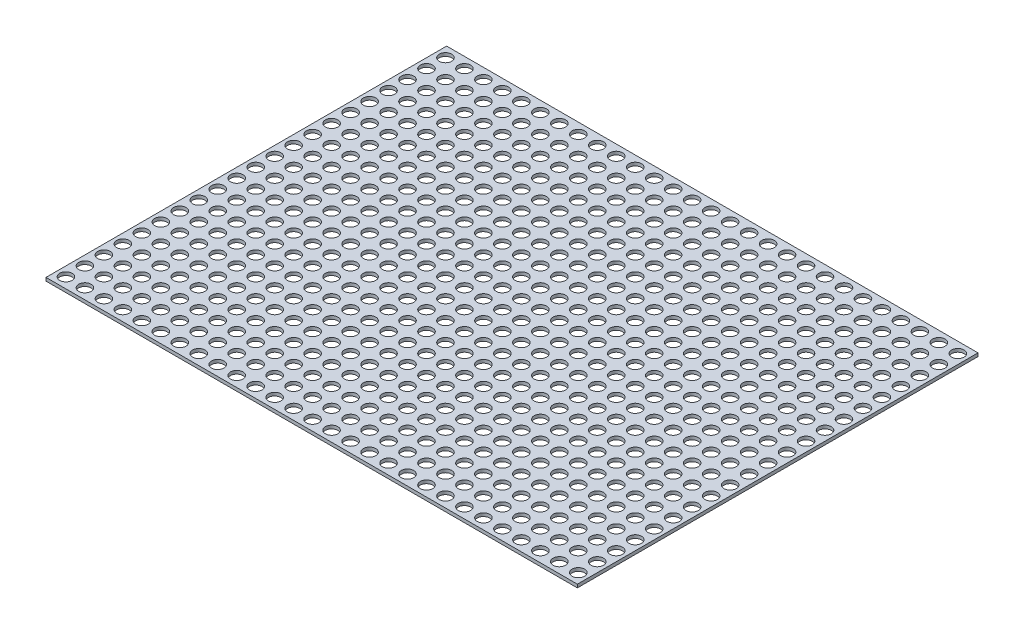
SolidWorks part; units mm, degrees
ref_plane "Front Plane" through (0, 0, 0) normal (0, 0, 1) x (1, 0, 0)
ref_plane "Top Plane" through (0, 0, 0) normal (0, 1, 0) x (1, 0, 0)
ref_plane "Right Plane" through (0, 0, 0) normal (1, 0, 0) x (0, 0, -1)
sketch "Sketch1" plane through (0, 0, 0) normal (0, 1, 0) x (1, 0, 0)
  line L0 (4.5, 4.95) -> (13.5, 4.95) construction
  line L1 (0, 0) -> (252, 0)
  line L2 (0, 0) -> (0, 190)
  line L3 (0, 190) -> (252, 190)
  line L4 (252, 0) -> (252, 190)
  line L5 (4.5, 4.95) -> (4.5, 13.95) construction
  circle A0 centre (4.5, 4.95) radius 2.95
  circle A1 centre (13.5, 4.95) radius 2.95
  circle A2 centre (22.5, 4.95) radius 2.95
  circle A3 centre (31.5, 4.95) radius 2.95
  circle A4 centre (40.5, 4.95) radius 2.95
  circle A5 centre (49.5, 4.95) radius 2.95
  circle A6 centre (58.5, 4.95) radius 2.95
  circle A7 centre (67.5, 4.95) radius 2.95
  circle A8 centre (76.5, 4.95) radius 2.95
  circle A9 centre (85.5, 4.95) radius 2.95
  circle A10 centre (94.5, 4.95) radius 2.95
  circle A11 centre (103.5, 4.95) radius 2.95
  circle A12 centre (112.5, 4.95) radius 2.95
  circle A13 centre (121.5, 4.95) radius 2.95
  circle A14 centre (130.5, 4.95) radius 2.95
  circle A15 centre (139.5, 4.95) radius 2.95
  circle A16 centre (148.5, 4.95) radius 2.95
  circle A17 centre (157.5, 4.95) radius 2.95
  circle A18 centre (166.5, 4.95) radius 2.95
  circle A19 centre (175.5, 4.95) radius 2.95
  circle A20 centre (184.5, 4.95) radius 2.95
  circle A21 centre (193.5, 4.95) radius 2.95
  circle A22 centre (202.5, 4.95) radius 2.95
  circle A23 centre (211.5, 4.95) radius 2.95
  circle A24 centre (220.5, 4.95) radius 2.95
  circle A25 centre (229.5, 4.95) radius 2.95
  circle A26 centre (238.5, 4.95) radius 2.95
  circle A27 centre (247.5, 4.95) radius 2.95
  circle A28 centre (13.5, 13.95) radius 2.95
  circle A29 centre (22.5, 13.95) radius 2.95
  circle A30 centre (31.5, 13.95) radius 2.95
  circle A31 centre (40.5, 13.95) radius 2.95
  circle A32 centre (49.5, 13.95) radius 2.95
  circle A33 centre (58.5, 13.95) radius 2.95
  circle A34 centre (67.5, 13.95) radius 2.95
  circle A35 centre (76.5, 13.95) radius 2.95
  circle A36 centre (85.5, 13.95) radius 2.95
  circle A37 centre (94.5, 13.95) radius 2.95
  circle A38 centre (103.5, 13.95) radius 2.95
  circle A39 centre (112.5, 13.95) radius 2.95
  circle A40 centre (121.5, 13.95) radius 2.95
  circle A41 centre (130.5, 13.95) radius 2.95
  circle A42 centre (139.5, 13.95) radius 2.95
  circle A43 centre (148.5, 13.95) radius 2.95
  circle A44 centre (157.5, 13.95) radius 2.95
  circle A45 centre (166.5, 13.95) radius 2.95
  circle A46 centre (175.5, 13.95) radius 2.95
  circle A47 centre (184.5, 13.95) radius 2.95
  circle A48 centre (193.5, 13.95) radius 2.95
  circle A49 centre (202.5, 13.95) radius 2.95
  circle A50 centre (211.5, 13.95) radius 2.95
  circle A51 centre (220.5, 13.95) radius 2.95
  circle A52 centre (229.5, 13.95) radius 2.95
  circle A53 centre (238.5, 13.95) radius 2.95
  circle A54 centre (247.5, 13.95) radius 2.95
  circle A55 centre (13.5, 22.95) radius 2.95
  circle A56 centre (22.5, 22.95) radius 2.95
  circle A57 centre (31.5, 22.95) radius 2.95
  circle A58 centre (40.5, 22.95) radius 2.95
  circle A59 centre (49.5, 22.95) radius 2.95
  circle A60 centre (58.5, 22.95) radius 2.95
  circle A61 centre (67.5, 22.95) radius 2.95
  circle A62 centre (76.5, 22.95) radius 2.95
  circle A63 centre (85.5, 22.95) radius 2.95
  circle A64 centre (94.5, 22.95) radius 2.95
  circle A65 centre (103.5, 22.95) radius 2.95
  circle A66 centre (112.5, 22.95) radius 2.95
  circle A67 centre (121.5, 22.95) radius 2.95
  circle A68 centre (130.5, 22.95) radius 2.95
  circle A69 centre (139.5, 22.95) radius 2.95
  circle A70 centre (148.5, 22.95) radius 2.95
  circle A71 centre (157.5, 22.95) radius 2.95
  circle A72 centre (166.5, 22.95) radius 2.95
  circle A73 centre (175.5, 22.95) radius 2.95
  circle A74 centre (184.5, 22.95) radius 2.95
  circle A75 centre (193.5, 22.95) radius 2.95
  circle A76 centre (202.5, 22.95) radius 2.95
  circle A77 centre (211.5, 22.95) radius 2.95
  circle A78 centre (220.5, 22.95) radius 2.95
  circle A79 centre (229.5, 22.95) radius 2.95
  circle A80 centre (238.5, 22.95) radius 2.95
  circle A81 centre (247.5, 22.95) radius 2.95
  circle A82 centre (13.5, 31.95) radius 2.95
  circle A83 centre (22.5, 31.95) radius 2.95
  circle A84 centre (31.5, 31.95) radius 2.95
  circle A85 centre (40.5, 31.95) radius 2.95
  circle A86 centre (49.5, 31.95) radius 2.95
  circle A87 centre (58.5, 31.95) radius 2.95
  circle A88 centre (67.5, 31.95) radius 2.95
  circle A89 centre (76.5, 31.95) radius 2.95
  circle A90 centre (85.5, 31.95) radius 2.95
  circle A91 centre (94.5, 31.95) radius 2.95
  circle A92 centre (103.5, 31.95) radius 2.95
  circle A93 centre (112.5, 31.95) radius 2.95
  circle A94 centre (121.5, 31.95) radius 2.95
  circle A95 centre (130.5, 31.95) radius 2.95
  circle A96 centre (139.5, 31.95) radius 2.95
  circle A97 centre (148.5, 31.95) radius 2.95
  circle A98 centre (157.5, 31.95) radius 2.95
  circle A99 centre (166.5, 31.95) radius 2.95
  circle A100 centre (175.5, 31.95) radius 2.95
  circle A101 centre (184.5, 31.95) radius 2.95
  circle A102 centre (193.5, 31.95) radius 2.95
  circle A103 centre (202.5, 31.95) radius 2.95
  circle A104 centre (211.5, 31.95) radius 2.95
  circle A105 centre (220.5, 31.95) radius 2.95
  circle A106 centre (229.5, 31.95) radius 2.95
  circle A107 centre (238.5, 31.95) radius 2.95
  circle A108 centre (247.5, 31.95) radius 2.95
  circle A109 centre (13.5, 40.95) radius 2.95
  circle A110 centre (22.5, 40.95) radius 2.95
  circle A111 centre (31.5, 40.95) radius 2.95
  circle A112 centre (40.5, 40.95) radius 2.95
  circle A113 centre (49.5, 40.95) radius 2.95
  circle A114 centre (58.5, 40.95) radius 2.95
  circle A115 centre (67.5, 40.95) radius 2.95
  circle A116 centre (76.5, 40.95) radius 2.95
  circle A117 centre (85.5, 40.95) radius 2.95
  circle A118 centre (94.5, 40.95) radius 2.95
  circle A119 centre (103.5, 40.95) radius 2.95
  circle A120 centre (112.5, 40.95) radius 2.95
  circle A121 centre (121.5, 40.95) radius 2.95
  circle A122 centre (130.5, 40.95) radius 2.95
  circle A123 centre (139.5, 40.95) radius 2.95
  circle A124 centre (148.5, 40.95) radius 2.95
  circle A125 centre (157.5, 40.95) radius 2.95
  circle A126 centre (166.5, 40.95) radius 2.95
  circle A127 centre (175.5, 40.95) radius 2.95
  circle A128 centre (184.5, 40.95) radius 2.95
  circle A129 centre (193.5, 40.95) radius 2.95
  circle A130 centre (202.5, 40.95) radius 2.95
  circle A131 centre (211.5, 40.95) radius 2.95
  circle A132 centre (220.5, 40.95) radius 2.95
  circle A133 centre (229.5, 40.95) radius 2.95
  circle A134 centre (238.5, 40.95) radius 2.95
  circle A135 centre (247.5, 40.95) radius 2.95
  circle A136 centre (13.5, 49.95) radius 2.95
  circle A137 centre (22.5, 49.95) radius 2.95
  circle A138 centre (31.5, 49.95) radius 2.95
  circle A139 centre (40.5, 49.95) radius 2.95
  circle A140 centre (49.5, 49.95) radius 2.95
  circle A141 centre (58.5, 49.95) radius 2.95
  circle A142 centre (67.5, 49.95) radius 2.95
  circle A143 centre (76.5, 49.95) radius 2.95
  circle A144 centre (85.5, 49.95) radius 2.95
  circle A145 centre (94.5, 49.95) radius 2.95
  circle A146 centre (103.5, 49.95) radius 2.95
  circle A147 centre (112.5, 49.95) radius 2.95
  circle A148 centre (121.5, 49.95) radius 2.95
  circle A149 centre (130.5, 49.95) radius 2.95
  circle A150 centre (139.5, 49.95) radius 2.95
  circle A151 centre (148.5, 49.95) radius 2.95
  circle A152 centre (157.5, 49.95) radius 2.95
  circle A153 centre (166.5, 49.95) radius 2.95
  circle A154 centre (175.5, 49.95) radius 2.95
  circle A155 centre (184.5, 49.95) radius 2.95
  circle A156 centre (193.5, 49.95) radius 2.95
  circle A157 centre (202.5, 49.95) radius 2.95
  circle A158 centre (211.5, 49.95) radius 2.95
  circle A159 centre (220.5, 49.95) radius 2.95
  circle A160 centre (229.5, 49.95) radius 2.95
  circle A161 centre (238.5, 49.95) radius 2.95
  circle A162 centre (247.5, 49.95) radius 2.95
  circle A163 centre (13.5, 58.95) radius 2.95
  circle A164 centre (22.5, 58.95) radius 2.95
  circle A165 centre (31.5, 58.95) radius 2.95
  circle A166 centre (40.5, 58.95) radius 2.95
  circle A167 centre (49.5, 58.95) radius 2.95
  circle A168 centre (58.5, 58.95) radius 2.95
  circle A169 centre (67.5, 58.95) radius 2.95
  circle A170 centre (76.5, 58.95) radius 2.95
  circle A171 centre (85.5, 58.95) radius 2.95
  circle A172 centre (94.5, 58.95) radius 2.95
  circle A173 centre (103.5, 58.95) radius 2.95
  circle A174 centre (112.5, 58.95) radius 2.95
  circle A175 centre (121.5, 58.95) radius 2.95
  circle A176 centre (130.5, 58.95) radius 2.95
  circle A177 centre (139.5, 58.95) radius 2.95
  circle A178 centre (148.5, 58.95) radius 2.95
  circle A179 centre (157.5, 58.95) radius 2.95
  circle A180 centre (166.5, 58.95) radius 2.95
  circle A181 centre (175.5, 58.95) radius 2.95
  circle A182 centre (184.5, 58.95) radius 2.95
  circle A183 centre (193.5, 58.95) radius 2.95
  circle A184 centre (202.5, 58.95) radius 2.95
  circle A185 centre (211.5, 58.95) radius 2.95
  circle A186 centre (220.5, 58.95) radius 2.95
  circle A187 centre (229.5, 58.95) radius 2.95
  circle A188 centre (238.5, 58.95) radius 2.95
  circle A189 centre (247.5, 58.95) radius 2.95
  circle A190 centre (13.5, 67.95) radius 2.95
  circle A191 centre (22.5, 67.95) radius 2.95
  circle A192 centre (31.5, 67.95) radius 2.95
  circle A193 centre (40.5, 67.95) radius 2.95
  circle A194 centre (49.5, 67.95) radius 2.95
  circle A195 centre (58.5, 67.95) radius 2.95
  circle A196 centre (67.5, 67.95) radius 2.95
  circle A197 centre (76.5, 67.95) radius 2.95
  circle A198 centre (85.5, 67.95) radius 2.95
  circle A199 centre (94.5, 67.95) radius 2.95
  circle A200 centre (103.5, 67.95) radius 2.95
  circle A201 centre (112.5, 67.95) radius 2.95
  circle A202 centre (121.5, 67.95) radius 2.95
  circle A203 centre (130.5, 67.95) radius 2.95
  circle A204 centre (139.5, 67.95) radius 2.95
  circle A205 centre (148.5, 67.95) radius 2.95
  circle A206 centre (157.5, 67.95) radius 2.95
  circle A207 centre (166.5, 67.95) radius 2.95
  circle A208 centre (175.5, 67.95) radius 2.95
  circle A209 centre (184.5, 67.95) radius 2.95
  circle A210 centre (193.5, 67.95) radius 2.95
  circle A211 centre (202.5, 67.95) radius 2.95
  circle A212 centre (211.5, 67.95) radius 2.95
  circle A213 centre (220.5, 67.95) radius 2.95
  circle A214 centre (229.5, 67.95) radius 2.95
  circle A215 centre (238.5, 67.95) radius 2.95
  circle A216 centre (247.5, 67.95) radius 2.95
  circle A217 centre (13.5, 76.95) radius 2.95
  circle A218 centre (22.5, 76.95) radius 2.95
  circle A219 centre (31.5, 76.95) radius 2.95
  circle A220 centre (40.5, 76.95) radius 2.95
  circle A221 centre (49.5, 76.95) radius 2.95
  circle A222 centre (58.5, 76.95) radius 2.95
  circle A223 centre (67.5, 76.95) radius 2.95
  circle A224 centre (76.5, 76.95) radius 2.95
  circle A225 centre (85.5, 76.95) radius 2.95
  circle A226 centre (94.5, 76.95) radius 2.95
  circle A227 centre (103.5, 76.95) radius 2.95
  circle A228 centre (112.5, 76.95) radius 2.95
  circle A229 centre (121.5, 76.95) radius 2.95
  circle A230 centre (130.5, 76.95) radius 2.95
  circle A231 centre (139.5, 76.95) radius 2.95
  circle A232 centre (148.5, 76.95) radius 2.95
  circle A233 centre (157.5, 76.95) radius 2.95
  circle A234 centre (166.5, 76.95) radius 2.95
  circle A235 centre (175.5, 76.95) radius 2.95
  circle A236 centre (184.5, 76.95) radius 2.95
  circle A237 centre (193.5, 76.95) radius 2.95
  circle A238 centre (202.5, 76.95) radius 2.95
  circle A239 centre (211.5, 76.95) radius 2.95
  circle A240 centre (220.5, 76.95) radius 2.95
  circle A241 centre (229.5, 76.95) radius 2.95
  circle A242 centre (238.5, 76.95) radius 2.95
  circle A243 centre (247.5, 76.95) radius 2.95
  circle A244 centre (13.5, 85.95) radius 2.95
  circle A245 centre (22.5, 85.95) radius 2.95
  circle A246 centre (31.5, 85.95) radius 2.95
  circle A247 centre (40.5, 85.95) radius 2.95
  circle A248 centre (49.5, 85.95) radius 2.95
  circle A249 centre (58.5, 85.95) radius 2.95
  circle A250 centre (67.5, 85.95) radius 2.95
  circle A251 centre (76.5, 85.95) radius 2.95
  circle A252 centre (85.5, 85.95) radius 2.95
  circle A253 centre (94.5, 85.95) radius 2.95
  circle A254 centre (103.5, 85.95) radius 2.95
  circle A255 centre (112.5, 85.95) radius 2.95
  circle A256 centre (121.5, 85.95) radius 2.95
  circle A257 centre (130.5, 85.95) radius 2.95
  circle A258 centre (139.5, 85.95) radius 2.95
  circle A259 centre (148.5, 85.95) radius 2.95
  circle A260 centre (157.5, 85.95) radius 2.95
  circle A261 centre (166.5, 85.95) radius 2.95
  circle A262 centre (175.5, 85.95) radius 2.95
  circle A263 centre (184.5, 85.95) radius 2.95
  circle A264 centre (193.5, 85.95) radius 2.95
  circle A265 centre (202.5, 85.95) radius 2.95
  circle A266 centre (211.5, 85.95) radius 2.95
  circle A267 centre (220.5, 85.95) radius 2.95
  circle A268 centre (229.5, 85.95) radius 2.95
  circle A269 centre (238.5, 85.95) radius 2.95
  circle A270 centre (247.5, 85.95) radius 2.95
  circle A271 centre (13.5, 94.95) radius 2.95
  circle A272 centre (22.5, 94.95) radius 2.95
  circle A273 centre (31.5, 94.95) radius 2.95
  circle A274 centre (40.5, 94.95) radius 2.95
  circle A275 centre (49.5, 94.95) radius 2.95
  circle A276 centre (58.5, 94.95) radius 2.95
  circle A277 centre (67.5, 94.95) radius 2.95
  circle A278 centre (76.5, 94.95) radius 2.95
  circle A279 centre (85.5, 94.95) radius 2.95
  circle A280 centre (94.5, 94.95) radius 2.95
  circle A281 centre (103.5, 94.95) radius 2.95
  circle A282 centre (112.5, 94.95) radius 2.95
  circle A283 centre (121.5, 94.95) radius 2.95
  circle A284 centre (130.5, 94.95) radius 2.95
  circle A285 centre (139.5, 94.95) radius 2.95
  circle A286 centre (148.5, 94.95) radius 2.95
  circle A287 centre (157.5, 94.95) radius 2.95
  circle A288 centre (166.5, 94.95) radius 2.95
  circle A289 centre (175.5, 94.95) radius 2.95
  circle A290 centre (184.5, 94.95) radius 2.95
  circle A291 centre (193.5, 94.95) radius 2.95
  circle A292 centre (202.5, 94.95) radius 2.95
  circle A293 centre (211.5, 94.95) radius 2.95
  circle A294 centre (220.5, 94.95) radius 2.95
  circle A295 centre (229.5, 94.95) radius 2.95
  circle A296 centre (238.5, 94.95) radius 2.95
  circle A297 centre (247.5, 94.95) radius 2.95
  circle A298 centre (13.5, 103.95) radius 2.95
  circle A299 centre (22.5, 103.95) radius 2.95
  circle A300 centre (31.5, 103.95) radius 2.95
  circle A301 centre (40.5, 103.95) radius 2.95
  circle A302 centre (49.5, 103.95) radius 2.95
  circle A303 centre (58.5, 103.95) radius 2.95
  circle A304 centre (67.5, 103.95) radius 2.95
  circle A305 centre (76.5, 103.95) radius 2.95
  circle A306 centre (85.5, 103.95) radius 2.95
  circle A307 centre (94.5, 103.95) radius 2.95
  circle A308 centre (103.5, 103.95) radius 2.95
  circle A309 centre (112.5, 103.95) radius 2.95
  circle A310 centre (121.5, 103.95) radius 2.95
  circle A311 centre (130.5, 103.95) radius 2.95
  circle A312 centre (139.5, 103.95) radius 2.95
  circle A313 centre (148.5, 103.95) radius 2.95
  circle A314 centre (157.5, 103.95) radius 2.95
  circle A315 centre (166.5, 103.95) radius 2.95
  circle A316 centre (175.5, 103.95) radius 2.95
  circle A317 centre (184.5, 103.95) radius 2.95
  circle A318 centre (193.5, 103.95) radius 2.95
  circle A319 centre (202.5, 103.95) radius 2.95
  circle A320 centre (211.5, 103.95) radius 2.95
  circle A321 centre (220.5, 103.95) radius 2.95
  circle A322 centre (229.5, 103.95) radius 2.95
  circle A323 centre (238.5, 103.95) radius 2.95
  circle A324 centre (247.5, 103.95) radius 2.95
  circle A325 centre (13.5, 112.95) radius 2.95
  circle A326 centre (22.5, 112.95) radius 2.95
  circle A327 centre (31.5, 112.95) radius 2.95
  circle A328 centre (40.5, 112.95) radius 2.95
  circle A329 centre (49.5, 112.95) radius 2.95
  circle A330 centre (58.5, 112.95) radius 2.95
  circle A331 centre (67.5, 112.95) radius 2.95
  circle A332 centre (76.5, 112.95) radius 2.95
  circle A333 centre (85.5, 112.95) radius 2.95
  circle A334 centre (94.5, 112.95) radius 2.95
  circle A335 centre (103.5, 112.95) radius 2.95
  circle A336 centre (112.5, 112.95) radius 2.95
  circle A337 centre (121.5, 112.95) radius 2.95
  circle A338 centre (130.5, 112.95) radius 2.95
  circle A339 centre (139.5, 112.95) radius 2.95
  circle A340 centre (148.5, 112.95) radius 2.95
  circle A341 centre (157.5, 112.95) radius 2.95
  circle A342 centre (166.5, 112.95) radius 2.95
  circle A343 centre (175.5, 112.95) radius 2.95
  circle A344 centre (184.5, 112.95) radius 2.95
  circle A345 centre (193.5, 112.95) radius 2.95
  circle A346 centre (202.5, 112.95) radius 2.95
  circle A347 centre (211.5, 112.95) radius 2.95
  circle A348 centre (220.5, 112.95) radius 2.95
  circle A349 centre (229.5, 112.95) radius 2.95
  circle A350 centre (238.5, 112.95) radius 2.95
  circle A351 centre (247.5, 112.95) radius 2.95
  circle A352 centre (13.5, 121.95) radius 2.95
  circle A353 centre (22.5, 121.95) radius 2.95
  circle A354 centre (31.5, 121.95) radius 2.95
  circle A355 centre (40.5, 121.95) radius 2.95
  circle A356 centre (49.5, 121.95) radius 2.95
  circle A357 centre (58.5, 121.95) radius 2.95
  circle A358 centre (67.5, 121.95) radius 2.95
  circle A359 centre (76.5, 121.95) radius 2.95
  circle A360 centre (85.5, 121.95) radius 2.95
  circle A361 centre (94.5, 121.95) radius 2.95
  circle A362 centre (103.5, 121.95) radius 2.95
  circle A363 centre (112.5, 121.95) radius 2.95
  circle A364 centre (121.5, 121.95) radius 2.95
  circle A365 centre (130.5, 121.95) radius 2.95
  circle A366 centre (139.5, 121.95) radius 2.95
  circle A367 centre (148.5, 121.95) radius 2.95
  circle A368 centre (157.5, 121.95) radius 2.95
  circle A369 centre (166.5, 121.95) radius 2.95
  circle A370 centre (175.5, 121.95) radius 2.95
  circle A371 centre (184.5, 121.95) radius 2.95
  circle A372 centre (193.5, 121.95) radius 2.95
  circle A373 centre (202.5, 121.95) radius 2.95
  circle A374 centre (211.5, 121.95) radius 2.95
  circle A375 centre (220.5, 121.95) radius 2.95
  circle A376 centre (229.5, 121.95) radius 2.95
  circle A377 centre (238.5, 121.95) radius 2.95
  circle A378 centre (247.5, 121.95) radius 2.95
  circle A379 centre (13.5, 130.95) radius 2.95
  circle A380 centre (22.5, 130.95) radius 2.95
  circle A381 centre (31.5, 130.95) radius 2.95
  circle A382 centre (40.5, 130.95) radius 2.95
  circle A383 centre (49.5, 130.95) radius 2.95
  circle A384 centre (58.5, 130.95) radius 2.95
  circle A385 centre (67.5, 130.95) radius 2.95
  circle A386 centre (76.5, 130.95) radius 2.95
  circle A387 centre (85.5, 130.95) radius 2.95
  circle A388 centre (94.5, 130.95) radius 2.95
  circle A389 centre (103.5, 130.95) radius 2.95
  circle A390 centre (112.5, 130.95) radius 2.95
  circle A391 centre (121.5, 130.95) radius 2.95
  circle A392 centre (130.5, 130.95) radius 2.95
  circle A393 centre (139.5, 130.95) radius 2.95
  circle A394 centre (148.5, 130.95) radius 2.95
  circle A395 centre (157.5, 130.95) radius 2.95
  circle A396 centre (166.5, 130.95) radius 2.95
  circle A397 centre (175.5, 130.95) radius 2.95
  circle A398 centre (184.5, 130.95) radius 2.95
  circle A399 centre (193.5, 130.95) radius 2.95
  circle A400 centre (202.5, 130.95) radius 2.95
  circle A401 centre (211.5, 130.95) radius 2.95
  circle A402 centre (220.5, 130.95) radius 2.95
  circle A403 centre (229.5, 130.95) radius 2.95
  circle A404 centre (238.5, 130.95) radius 2.95
  circle A405 centre (247.5, 130.95) radius 2.95
  circle A406 centre (13.5, 139.95) radius 2.95
  circle A407 centre (22.5, 139.95) radius 2.95
  circle A408 centre (31.5, 139.95) radius 2.95
  circle A409 centre (40.5, 139.95) radius 2.95
  circle A410 centre (49.5, 139.95) radius 2.95
  circle A411 centre (58.5, 139.95) radius 2.95
  circle A412 centre (67.5, 139.95) radius 2.95
  circle A413 centre (76.5, 139.95) radius 2.95
  circle A414 centre (85.5, 139.95) radius 2.95
  circle A415 centre (94.5, 139.95) radius 2.95
  circle A416 centre (103.5, 139.95) radius 2.95
  circle A417 centre (112.5, 139.95) radius 2.95
  circle A418 centre (121.5, 139.95) radius 2.95
  circle A419 centre (130.5, 139.95) radius 2.95
  circle A420 centre (139.5, 139.95) radius 2.95
  circle A421 centre (148.5, 139.95) radius 2.95
  circle A422 centre (157.5, 139.95) radius 2.95
  circle A423 centre (166.5, 139.95) radius 2.95
  circle A424 centre (175.5, 139.95) radius 2.95
  circle A425 centre (184.5, 139.95) radius 2.95
  circle A426 centre (193.5, 139.95) radius 2.95
  circle A427 centre (202.5, 139.95) radius 2.95
  circle A428 centre (211.5, 139.95) radius 2.95
  circle A429 centre (220.5, 139.95) radius 2.95
  circle A430 centre (229.5, 139.95) radius 2.95
  circle A431 centre (238.5, 139.95) radius 2.95
  circle A432 centre (247.5, 139.95) radius 2.95
  circle A433 centre (13.5, 148.95) radius 2.95
  circle A434 centre (22.5, 148.95) radius 2.95
  circle A435 centre (31.5, 148.95) radius 2.95
  circle A436 centre (40.5, 148.95) radius 2.95
  circle A437 centre (49.5, 148.95) radius 2.95
  circle A438 centre (58.5, 148.95) radius 2.95
  circle A439 centre (67.5, 148.95) radius 2.95
  circle A440 centre (76.5, 148.95) radius 2.95
  circle A441 centre (85.5, 148.95) radius 2.95
  circle A442 centre (94.5, 148.95) radius 2.95
  circle A443 centre (103.5, 148.95) radius 2.95
  circle A444 centre (112.5, 148.95) radius 2.95
  circle A445 centre (121.5, 148.95) radius 2.95
  circle A446 centre (130.5, 148.95) radius 2.95
  circle A447 centre (139.5, 148.95) radius 2.95
  circle A448 centre (148.5, 148.95) radius 2.95
  circle A449 centre (157.5, 148.95) radius 2.95
  circle A450 centre (166.5, 148.95) radius 2.95
  circle A451 centre (175.5, 148.95) radius 2.95
  circle A452 centre (184.5, 148.95) radius 2.95
  circle A453 centre (193.5, 148.95) radius 2.95
  circle A454 centre (202.5, 148.95) radius 2.95
  circle A455 centre (211.5, 148.95) radius 2.95
  circle A456 centre (220.5, 148.95) radius 2.95
  circle A457 centre (229.5, 148.95) radius 2.95
  circle A458 centre (238.5, 148.95) radius 2.95
  circle A459 centre (247.5, 148.95) radius 2.95
  circle A460 centre (13.5, 157.95) radius 2.95
  circle A461 centre (22.5, 157.95) radius 2.95
  circle A462 centre (31.5, 157.95) radius 2.95
  circle A463 centre (40.5, 157.95) radius 2.95
  circle A464 centre (49.5, 157.95) radius 2.95
  circle A465 centre (58.5, 157.95) radius 2.95
  circle A466 centre (67.5, 157.95) radius 2.95
  circle A467 centre (76.5, 157.95) radius 2.95
  circle A468 centre (85.5, 157.95) radius 2.95
  circle A469 centre (94.5, 157.95) radius 2.95
  circle A470 centre (103.5, 157.95) radius 2.95
  circle A471 centre (112.5, 157.95) radius 2.95
  circle A472 centre (121.5, 157.95) radius 2.95
  circle A473 centre (130.5, 157.95) radius 2.95
  circle A474 centre (139.5, 157.95) radius 2.95
  circle A475 centre (148.5, 157.95) radius 2.95
  circle A476 centre (157.5, 157.95) radius 2.95
  circle A477 centre (166.5, 157.95) radius 2.95
  circle A478 centre (175.5, 157.95) radius 2.95
  circle A479 centre (184.5, 157.95) radius 2.95
  circle A480 centre (193.5, 157.95) radius 2.95
  circle A481 centre (202.5, 157.95) radius 2.95
  circle A482 centre (211.5, 157.95) radius 2.95
  circle A483 centre (220.5, 157.95) radius 2.95
  circle A484 centre (229.5, 157.95) radius 2.95
  circle A485 centre (238.5, 157.95) radius 2.95
  circle A486 centre (247.5, 157.95) radius 2.95
  circle A487 centre (13.5, 166.95) radius 2.95
  circle A488 centre (22.5, 166.95) radius 2.95
  circle A489 centre (31.5, 166.95) radius 2.95
  circle A490 centre (40.5, 166.95) radius 2.95
  circle A491 centre (49.5, 166.95) radius 2.95
  circle A492 centre (58.5, 166.95) radius 2.95
  circle A493 centre (67.5, 166.95) radius 2.95
  circle A494 centre (76.5, 166.95) radius 2.95
  circle A495 centre (85.5, 166.95) radius 2.95
  circle A496 centre (94.5, 166.95) radius 2.95
  circle A497 centre (103.5, 166.95) radius 2.95
  circle A498 centre (112.5, 166.95) radius 2.95
  circle A499 centre (121.5, 166.95) radius 2.95
  circle A500 centre (130.5, 166.95) radius 2.95
  circle A501 centre (139.5, 166.95) radius 2.95
  circle A502 centre (148.5, 166.95) radius 2.95
  circle A503 centre (157.5, 166.95) radius 2.95
  circle A504 centre (166.5, 166.95) radius 2.95
  circle A505 centre (175.5, 166.95) radius 2.95
  circle A506 centre (184.5, 166.95) radius 2.95
  circle A507 centre (193.5, 166.95) radius 2.95
  circle A508 centre (202.5, 166.95) radius 2.95
  circle A509 centre (211.5, 166.95) radius 2.95
  circle A510 centre (220.5, 166.95) radius 2.95
  circle A511 centre (229.5, 166.95) radius 2.95
  circle A512 centre (238.5, 166.95) radius 2.95
  circle A513 centre (247.5, 166.95) radius 2.95
  circle A514 centre (13.5, 175.95) radius 2.95
  circle A515 centre (22.5, 175.95) radius 2.95
  circle A516 centre (31.5, 175.95) radius 2.95
  circle A517 centre (40.5, 175.95) radius 2.95
  circle A518 centre (49.5, 175.95) radius 2.95
  circle A519 centre (58.5, 175.95) radius 2.95
  circle A520 centre (67.5, 175.95) radius 2.95
  circle A521 centre (76.5, 175.95) radius 2.95
  circle A522 centre (85.5, 175.95) radius 2.95
  circle A523 centre (94.5, 175.95) radius 2.95
  circle A524 centre (103.5, 175.95) radius 2.95
  circle A525 centre (112.5, 175.95) radius 2.95
  circle A526 centre (121.5, 175.95) radius 2.95
  circle A527 centre (130.5, 175.95) radius 2.95
  circle A528 centre (139.5, 175.95) radius 2.95
  circle A529 centre (148.5, 175.95) radius 2.95
  circle A530 centre (157.5, 175.95) radius 2.95
  circle A531 centre (166.5, 175.95) radius 2.95
  circle A532 centre (175.5, 175.95) radius 2.95
  circle A533 centre (184.5, 175.95) radius 2.95
  circle A534 centre (193.5, 175.95) radius 2.95
  circle A535 centre (202.5, 175.95) radius 2.95
  circle A536 centre (211.5, 175.95) radius 2.95
  circle A537 centre (220.5, 175.95) radius 2.95
  circle A538 centre (229.5, 175.95) radius 2.95
  circle A539 centre (238.5, 175.95) radius 2.95
  circle A540 centre (247.5, 175.95) radius 2.95
  circle A541 centre (13.5, 184.95) radius 2.95
  circle A542 centre (22.5, 184.95) radius 2.95
  circle A543 centre (31.5, 184.95) radius 2.95
  circle A544 centre (40.5, 184.95) radius 2.95
  circle A545 centre (49.5, 184.95) radius 2.95
  circle A546 centre (58.5, 184.95) radius 2.95
  circle A547 centre (67.5, 184.95) radius 2.95
  circle A548 centre (76.5, 184.95) radius 2.95
  circle A549 centre (85.5, 184.95) radius 2.95
  circle A550 centre (94.5, 184.95) radius 2.95
  circle A551 centre (103.5, 184.95) radius 2.95
  circle A552 centre (112.5, 184.95) radius 2.95
  circle A553 centre (121.5, 184.95) radius 2.95
  circle A554 centre (130.5, 184.95) radius 2.95
  circle A555 centre (139.5, 184.95) radius 2.95
  circle A556 centre (148.5, 184.95) radius 2.95
  circle A557 centre (157.5, 184.95) radius 2.95
  circle A558 centre (166.5, 184.95) radius 2.95
  circle A559 centre (175.5, 184.95) radius 2.95
  circle A560 centre (184.5, 184.95) radius 2.95
  circle A561 centre (193.5, 184.95) radius 2.95
  circle A562 centre (202.5, 184.95) radius 2.95
  circle A563 centre (211.5, 184.95) radius 2.95
  circle A564 centre (220.5, 184.95) radius 2.95
  circle A565 centre (229.5, 184.95) radius 2.95
  circle A566 centre (238.5, 184.95) radius 2.95
  circle A567 centre (247.5, 184.95) radius 2.95
  circle A568 centre (4.5, 13.95) radius 2.95
  circle A569 centre (4.5, 22.95) radius 2.95
  circle A570 centre (4.5, 31.95) radius 2.95
  circle A571 centre (4.5, 40.95) radius 2.95
  circle A572 centre (4.5, 49.95) radius 2.95
  circle A573 centre (4.5, 58.95) radius 2.95
  circle A574 centre (4.5, 67.95) radius 2.95
  circle A575 centre (4.5, 76.95) radius 2.95
  circle A576 centre (4.5, 85.95) radius 2.95
  circle A577 centre (4.5, 94.95) radius 2.95
  circle A578 centre (4.5, 103.95) radius 2.95
  circle A579 centre (4.5, 112.95) radius 2.95
  circle A580 centre (4.5, 121.95) radius 2.95
  circle A581 centre (4.5, 130.95) radius 2.95
  circle A582 centre (4.5, 139.95) radius 2.95
  circle A583 centre (4.5, 148.95) radius 2.95
  circle A584 centre (4.5, 157.95) radius 2.95
  circle A585 centre (4.5, 166.95) radius 2.95
  circle A586 centre (4.5, 175.95) radius 2.95
  circle A587 centre (4.5, 184.95) radius 2.95
  dimension "D3" = 5.9
  dimension "D1" = 252
  dimension "D2" = 190
  dimension "D4" = 4.95
  dimension "D5" = 4.5
  dimension "D8" = 9
  dimension "D9" = 9
  dimension "D6" = 28
  dimension "D7" = 21
extrude "Boss-Extrude1" add sketch "Sketch1" along normal blind 1.55 contours L1 L4 L3 L2 A587 A586 A585 A584 A583 A582 A581 A580 A579 A578 A577 A576 A575 A574 A573 A572 A571 A570 A569 A568 A567 A566 A565 region at (126, 0, -95.0253)
equation "\"Length\" = 283mm"
equation "\"Width\" = 225mm"
equation "\"WallThickness\" = 12.5mm"
equation "\"UpperWaterJacketThickness\" = 28mm"
equation "\"SpacerHeight\" = 80.2mm"
equation "\"PlateLength\" = 252mm"
equation "\"D1@Sketch1\"=\"PlateLength\""
equation "\"PlateWidth\" = 190mm"
equation "\"D2@Sketch1\"=\"PlateWidth\""
equation "\"PlateHoleDiameter\" = 5.9mm"
equation "\"D3@Sketch1\"=\"PlateHoleDiameter\""
equation "\"PlateHoleBottom\" = 2mm"
equation "\"D4@Sketch1\"=\"PlateHoleBottom\"+\"PlateHoleDiameter\"/2"
equation "\"PlateHoleSide\" = 1.55mm"
equation "\"D5@Sketch1\"=\"PlateHoleSide\"+\"PlateHoleDiameter\"/2"
equation "\"PlateHoleSpacing\" = 3.1mm"
equation "\"D8@Sketch1\"=\"PlateHoleSpacing\"+\"PlateHoleDiameter\""
equation "\"D9@Sketch1\"=\"PlateHoleSpacing\"+\"PlateHoleDiameter\""
equation "\"PlateThickness\" = 1.55mm"
equation "\"D1@Boss-Extrude1\"=\"PlateThickness\""
